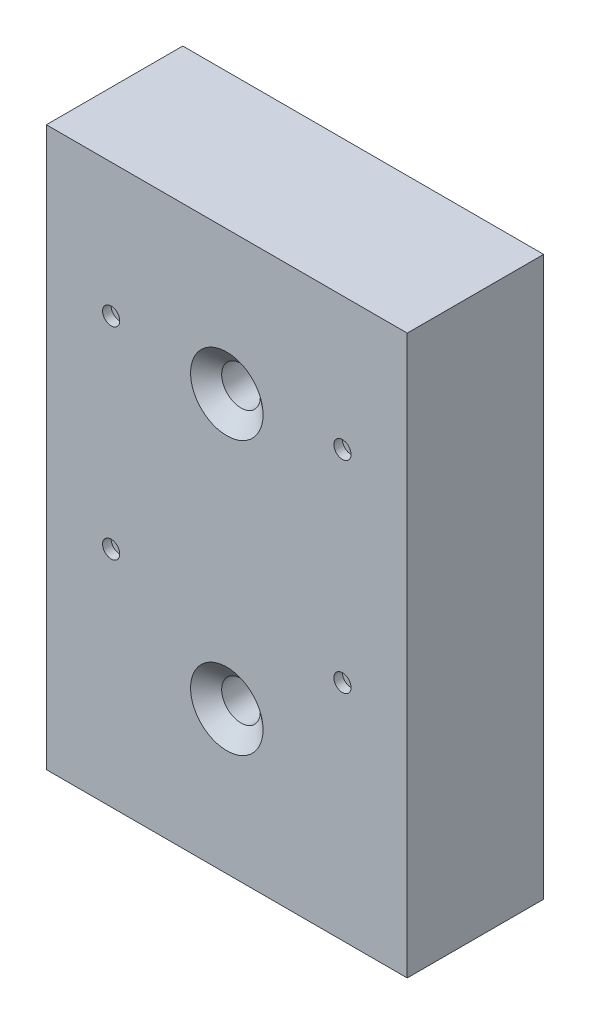
SolidWorks part; units mm, degrees
ref_plane "Front Plane" through (0, 0, 0) normal (0, 0, 1) x (1, 0, 0)
ref_plane "Top Plane" through (0, 0, 0) normal (0, 1, 0) x (1, 0, 0)
ref_plane "Right Plane" through (0, 0, 0) normal (1, 0, 0) x (0, 0, -1)
sketch "Sketch1" plane through (0, 0, 0) normal (0, 0, 1) x (1, 0, 0)
  line L1 (-21, 32.5) -> (21, 32.5)
  line L2 (-21, 32.5) -> (-21, -32.5)
  line L3 (-21, -32.5) -> (21, -32.5)
  line L4 (21, 32.5) -> (21, -32.5)
  line L5 (-21, 32.5) -> (21, -32.5) construction
  line L6 (-21, -32.5) -> (21, 32.5) construction
  point P0 (0, 0)
  dimension "D1" = 65
  dimension "D2" = 42
extrude "Boss-Extrude1" add sketch "Sketch1" along normal blind 15.875
sketch "Sketch2" plane through (0, 0, 15.875) normal (0, 0, 1) x (1, 0, 0)
  line L0 (0, 0) -> (0, -32.5) construction
  line L1 (-21, -32.5) -> (21, -32.5) construction
  circle A0 centre (-13.4595, -6.5) radius 1
  circle A1 centre (-13.4595, 17) radius 1
  circle A4 centre (13.4595, 17) radius 1
  circle A5 centre (13.4595, -6.5) radius 1
  dimension "D2" = 23.5
  dimension "D3" = 2
  dimension "D1" = 26
extrude "Cut-Extrude1" cut sketch "Sketch2" against normal blind 1 and the other way through all
hole_wizard "CSK for #8 Flat Head Machine Screw (100)1" positions "Sketch4" profile "Sketch3" countersink size "#8" standard "ANSI Inch" end condition through all
sketch "Sketch4" plane through (0, 0, 15.875) normal (0, 0, 1) x (1, 0, 0)
  line L0 (0, 0) -> (-21, 0) construction
  line L1 (-21, 32.5) -> (-21, -32.5) construction
  line L4 (0, 32.5) -> (0, -32.5) construction
  line L5 (21, 32.5) -> (-21, 32.5) construction
  line L6 (-21, -32.5) -> (21, -32.5) construction
  point P0 (0, 15.875)
  point P17 (0, -15.875)
  point P20 (0, 16.0124)
  point P21 (0, 0)
  dimension "D1" = 31.75
sketch "Sketch3" plane through (0, 15.875, 15.875) normal (1, 0, 0) x (0, -1, 0)
  line L0 (0, 0) -> (0, 15.875)
  line L1 (0, 15.875) -> (2.2479, 15.875)
  line L2 (2.2479, 15.875) -> (2.2479, 1.6518)
  line L3 (2.2479, 1.6518) -> (4.2164, 0)
  line L5 (4.2164, 0) -> (0, 0)
  line L6 (-2.2479, 1.6518) -> (-4.2164, 0) construction
  line L11 (0, -6.35) -> (0, 107.95) construction
  dimension "Thru Hole Dia." = 4.4958
  dimension "Thru Hole Depth" = 15.875
  dimension "Near C'Sink Dia." = 8.4328
  dimension "Near C'Sink Angle" = 100
